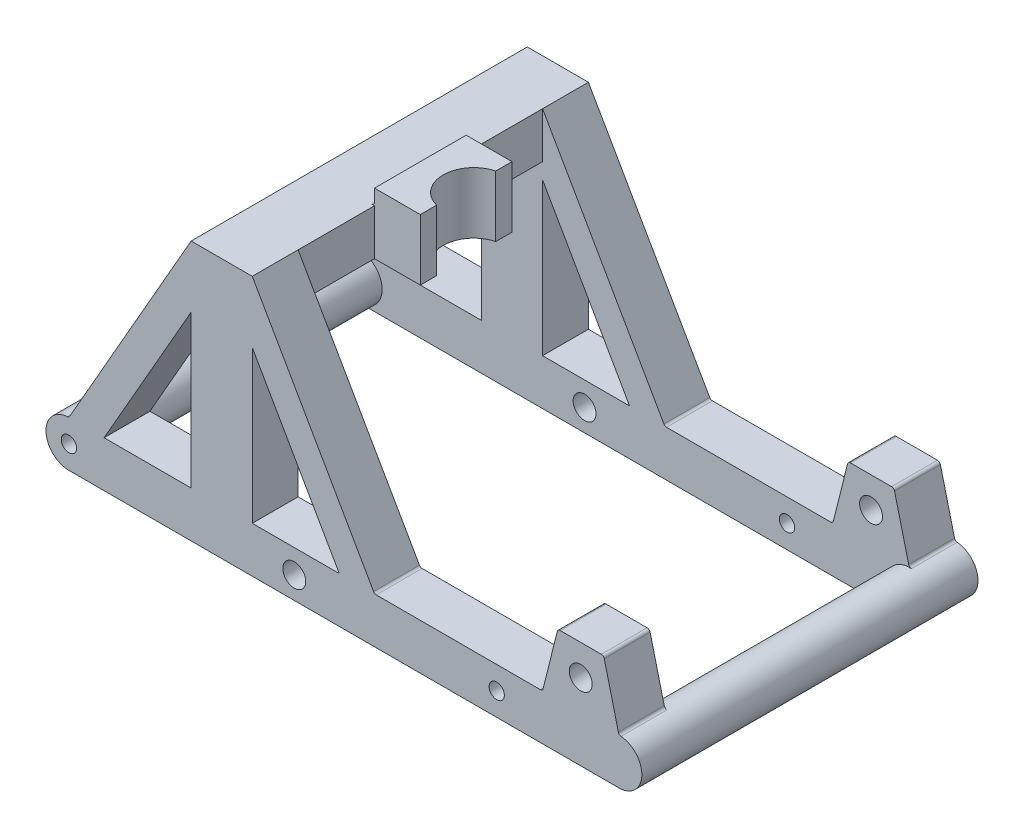
SolidWorks part; units mm, degrees
ref_plane "Front Plane" through (0, 0, 0) normal (0, 0, 1) x (1, 0, 0)
ref_plane "Top Plane" through (0, 0, 0) normal (0, 1, 0) x (1, 0, 0)
ref_plane "Right Plane" through (0, 0, 0) normal (1, 0, 0) x (0, 0, -1)
sketch "Sketch1" plane through (0, 0, 0) normal (0, 0, 1) x (1, 0, 0)
  line L6 (228.6, 38.1) -> (-228.6, 38.1)
  line L7 (-228.6, 0) -> (228.6, 0)
  circle A4 centre (-29.8574, -12.7) radius 57.15
  arc A7 (-228.6, 0) -> (-228.6, 38.1) centre (-228.6, 19.05) cw
  arc A8 (228.6, 0) -> (228.6, 38.1) centre (228.6, 19.05) ccw
  point P1 (0, 0)
  dimension "D1" = 38.1
  dimension "D2" = 457.2
extrude "Boss-Extrude1" add sketch "Sketch1" along normal blind 38.1
sketch "Sketch2" plane through (0, 0, 38.1) normal (0, 0, 1) x (1, 0, 0)
  circle A0 centre (-228.6, 19.05) radius 19.05
  circle A1 centre (228.6, 19.05) radius 19.05
  arc A2 (-228.6, 38.1) -> (-228.6, 0) centre (-228.6, 19.05) ccw construction
extrude "Boss-Extrude2" add sketch "Sketch2" along normal blind 203.2
ref_plane "Plane4" through (0, 0, 139.7) normal (0, 0, 1) x (1, 0, 0)
mirror "Mirror3" about plane through (0, 0, 139.7) normal (0, 0, 1) of "Boss-Extrude1", "Boss-Extrude2"
sketch "Sketch4" plane through (0, 38.1, 0) normal (0, 1, 0) x (1, 0, 0)
  line L5 (-228.6, -279.4) -> (-228.6, -241.3)
  line L6 (228.6, -279.4) -> (-228.6, -279.4) construction
  line L7 (-228.6, -241.3) -> (25.4, -241.3)
  line L8 (228.6, -241.3) -> (-228.6, -241.3) construction
  line L9 (25.4, -241.3) -> (25.4, -279.4)
  line L10 (25.4, -279.4) -> (-228.6, -279.4)
  line L12 (-228.6, -241.3) -> (-228.6, -279.4) construction
  dimension "D1" = 254
extrude "Boss-Extrude3" add sketch "Sketch4" along normal blind 177.8
sketch "Sketch7" plane through (0, 0, 279.4) normal (0, 0, 1) x (1, 0, 0)
  line L0 (-228.6, 38.1) -> (-127, 215.9)
  line L1 (-228.6, 215.9) -> (25.4, 215.9) construction
  line L2 (-76.2, 215.9) -> (25.4, 38.1)
  line L3 (-228.6, 38.1) -> (-228.6, 215.9)
  line L4 (-228.6, 215.9) -> (-127, 215.9)
  line L5 (-76.2, 215.9) -> (25.4, 215.9)
  line L6 (25.4, 215.9) -> (25.4, 38.1)
  line L7 (-127, 164.7047) -> (-199.3455, 38.1)
  line L8 (-199.3455, 38.1) -> (-127, 38.1)
  line L9 (-127, 38.1) -> (-127, 164.7047)
  line L10 (-76.2, 164.7047) -> (-76.2, 38.1)
  line L11 (-76.2, 38.1) -> (-3.8545, 38.1)
  line L12 (-3.8545, 38.1) -> (-76.2, 164.7047)
  dimension "D1" = 50.8
  dimension "D2" = 101.6
  dimension "D3" = 101.6
  dimension "D4" = 25.4
  dimension "D5" = 25.4
  dimension "D6" = 50.8
  dimension "D10" = 29.745
extrude "Cut-Extrude3" cut sketch "Sketch7" against normal blind 38.1
mirror "Mirror4" about plane through (0, 0, 139.7) normal (0, 0, 1) of "Cut-Extrude3", "Boss-Extrude3"
sketch "Sketch8" plane through (0, 0, 279.4) normal (0, 0, 1) x (1, 0, 0)
  line L1 (228.6, 38.1) -> (25.4, 38.1) construction
  circle A0 centre (-228.6, 19.05) radius 6.35
  circle A1 centre (127, 19.05) radius 6.35
  arc A2 (228.6, 0) -> (228.6, 38.1) centre (228.6, 19.05) ccw construction
  arc A3 (-228.6, 38.1) -> (-228.6, 0) centre (-228.6, 19.05) ccw construction
  point P7 (247.65, 19.05)
  point P18 (127, 38.1)
  dimension "D1" = 12.7
  dimension "D2" = 355.6
extrude "Cut-Extrude4" cut sketch "Sketch8" against normal through all
sketch "Sketch9" plane through (0, 0, 241.3) normal (0, 0, -1) x (-1, 0, 0)
  line L0 (76.2, 215.9) -> (76.2, 177.8)
  line L1 (76.2, 215.9) -> (127, 215.9) construction
  line L2 (76.2, 215.9) -> (-25.4, 38.1) construction
  line L3 (76.2, 177.8) -> (127, 177.8)
  line L4 (127, 177.8) -> (127, 215.9)
  line L5 (228.6, 38.1) -> (127, 215.9) construction
  line L6 (127, 215.9) -> (76.2, 215.9)
  dimension "D1" = 38.1
extrude "Boss-Extrude4" add sketch "Sketch9" along normal up to next
sketch "Sketch10" plane through (0, 177.8, 0) normal (0, -1, 0) x (1, 0, 0)
  line L0 (-76.2, 177.8) -> (-38.1, 177.8)
  line L1 (-76.2, 38.1) -> (-76.2, 241.3) construction
  line L2 (-38.1, 177.8) -> (-38.1, 164.2934)
  line L3 (-76.2, 101.6) -> (-38.1, 101.6)
  line L4 (-38.1, 101.6) -> (-38.1, 115.1066)
  line L5 (-228.6, 241.3) -> (228.6, 241.3) construction
  line L6 (-228.6, 38.1) -> (228.6, 38.1) construction
  line L7 (-76.2, 177.8) -> (-76.2, 101.6)
  arc A0 (-38.1, 164.2934) -> (-38.1, 115.1066) centre (-31.75, 139.7) ccw
  dimension "D6" = 50.8
  dimension "D1" = 6.35
  dimension "D2" = 38.1
  dimension "D3" = 63.5
  dimension "D4" = 38.1
  dimension "D5" = 63.5
extrude "Boss-Extrude5" add sketch "Sketch10" against normal blind 50.8 contours L0 L2 A0 L4 L3 L7
sketch "Sketch13" plane through (0, 38.1, 0) normal (0, 1, 0) x (1, 0, 0)
  line L0 (228.6, -279.4) -> (228.6, -241.3)
  line L2 (228.6, -241.3) -> (165.1, -241.3)
  line L3 (228.6, -241.3) -> (25.4, -241.3) construction
  line L4 (165.1, -241.3) -> (165.1, -279.4)
  line L5 (228.6, -279.4) -> (25.4, -279.4) construction
  line L6 (165.1, -279.4) -> (228.6, -279.4)
  line L7 (165.1, -38.1) -> (165.1, 0)
  line L8 (228.6, -38.1) -> (25.4, -38.1) construction
  line L9 (228.6, 0) -> (25.4, 0) construction
  line L10 (165.1, 0) -> (228.6, 0)
  line L11 (228.6, 0) -> (228.6, -38.1)
  line L12 (228.6, -38.1) -> (165.1, -38.1)
  dimension "D1" = 63.5
extrude "Boss-Extrude6" add sketch "Sketch13" along normal blind 50.8
sketch "Sketch14" plane through (0, 0, 0) normal (0, 0, -1) x (-1, 0, 0)
  line L0 (-177.8, 88.9) -> (-165.1, 38.1)
  line L1 (-228.6, 88.9) -> (-165.1, 88.9) construction
  line L2 (-228.6, 38.1) -> (-215.9, 88.9)
  line L3 (-228.6, 88.9) -> (-228.6, 38.1) construction
  line L4 (-215.9, 88.9) -> (-228.6, 88.9)
  line L5 (-228.6, 88.9) -> (-228.6, 38.1)
  line L6 (-177.8, 88.9) -> (-165.1, 88.9)
  line L7 (-165.1, 88.9) -> (-165.1, 38.1)
  arc A0 (-228.6, 38.1) -> (-228.6, 0) centre (-228.6, 19.05) ccw construction
  dimension "D1" = 12.7
  dimension "D2" = 12.7
extrude "Cut-Extrude7" cut sketch "Sketch14" against normal through all
fillet "Fillet1" radius 2.54 13 edges at (-76.2, 215.9, 139.7) (25.4, 38.1, 260.35) (25.4, 38.1, 19.05) (-228.6, 38.1, 260.35) (-228.6, 38.1, 19.05) (215.9, 88.9, 260.35) (177.8, 88.9, 260.35) (165.1, 38.1, 19.05) (165.1, 38.1, 260.35) (177.8, 88.9, 19.05) (215.9, 88.9, 19.05) (228.6, 38.1, 19.05) (228.6, 38.1, 260.35)
sketch "Sketch12" plane through (0, 0, 0) normal (0, 0, -1) x (-1, 0, 0)
  line L0 (-213.9168, 88.9) -> (-179.7832, 88.9) construction
  circle A0 centre (41.275, 18.3861) radius 9.525
  arc A1 (228.6, 0) -> (229.927, 38.0537) centre (228.6, 19.05) ccw construction
  circle A2 centre (-196.85, 63.5) radius 9.525
  point P5 (247.6384, 18.3861)
  point P12 (-196.85, 88.9)
  dimension "D1" = 19.05
  dimension "D3" = 19.05
  dimension "D2" = 34.925
  dimension "D4" = 25.4
extrude "Cut-Extrude5" cut sketch "Sketch12" against normal through all
